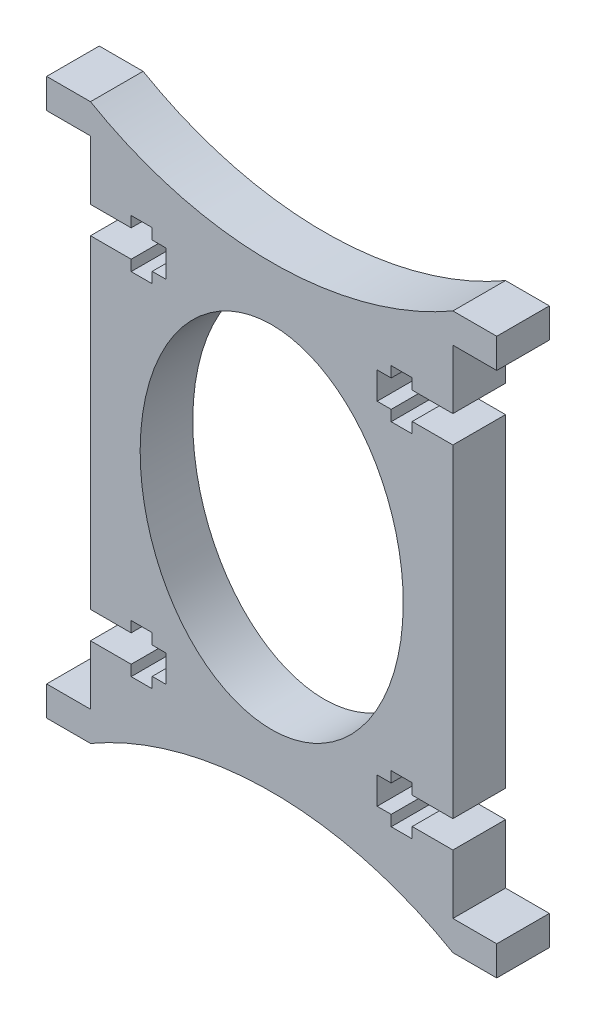
SolidWorks part; units mm, degrees
material "Acrylic (Medium-high impact)"
ref_plane "Front Plane" through (0, 0, 0) normal (0, 0, 1) x (1, 0, 0)
ref_plane "Top Plane" through (0, 0, 0) normal (0, 1, 0) x (1, 0, 0)
ref_plane "Right Plane" through (0, 0, 0) normal (1, 0, 0) x (0, 0, -1)
sketch "Sketch1" plane through (0, 0, 0) normal (0, 0, 1) x (1, 0, 0)
  line L0 (742.183, 459.4261) -> (700.8541, 459.4261) construction
  line L1 (737.5448, 439.4261) -> (742.183, 439.4261) construction
  line L2 (737.5448, 439.4261) -> (737.5448, 437.8782) construction
  line L3 (737.5448, 440.9739) -> (737.5448, 439.4261) construction
  line L4 (736.3448, 436.6538) -> (736.3448, 439.4261) construction
  line L5 (733.5448, 439.4261) -> (742.183, 439.4261) construction
  line L6 (736.3448, 442.1983) -> (736.3448, 439.4261) construction
  line L7 (735.1448, 436.6538) -> (737.5448, 436.6538)
  line L8 (700.8541, 459.4261) -> (700.8541, 440.9739)
  line L9 (706.6923, 442.1983) -> (706.6923, 439.4261) construction
  line L10 (735.1448, 442.1983) -> (737.5448, 442.1983)
  line L11 (733.5448, 440.9739) -> (733.5448, 437.8782)
  line L12 (742.183, 437.8782) -> (742.183, 431.1161)
  line L13 (742.183, 437.8782) -> (737.5448, 437.8782)
  line L14 (737.5448, 440.9739) -> (742.183, 440.9739)
  line L15 (747.183, 427.7361) -> (747.183, 431.1161)
  line L16 (742.183, 427.7361) -> (747.183, 427.7361)
  line L17 (709.4923, 439.4261) -> (700.8541, 439.4261) construction
  line L18 (707.8923, 436.6538) -> (707.8923, 437.8782)
  line L19 (707.8923, 440.9739) -> (709.4923, 440.9739)
  line L20 (707.8923, 437.8782) -> (709.4923, 437.8782)
  line L21 (707.8923, 440.9739) -> (707.8923, 442.1983)
  line L22 (706.6923, 436.6538) -> (706.6923, 439.4261) construction
  line L23 (705.4923, 436.6538) -> (705.4923, 437.8782)
  line L24 (705.4923, 440.9739) -> (705.4923, 442.1983)
  line L25 (705.4923, 440.9739) -> (705.4923, 439.4261) construction
  line L26 (705.4923, 439.4261) -> (705.4923, 437.8782) construction
  line L27 (695.8541, 431.1161) -> (700.8541, 431.1161)
  line L28 (700.8541, 427.7361) -> (695.8541, 427.7361)
  line L29 (695.8541, 427.7361) -> (695.8541, 431.1161)
  line L30 (705.4923, 440.9739) -> (700.8541, 440.9739)
  line L31 (700.8541, 437.8782) -> (705.4923, 437.8782)
  line L32 (700.8541, 437.8782) -> (700.8541, 431.1161)
  line L33 (705.4923, 439.4261) -> (700.8541, 439.4261) construction
  line L34 (709.4923, 440.9739) -> (709.4923, 437.8782)
  line L35 (747.183, 431.1161) -> (742.183, 431.1161)
  line L36 (737.5448, 440.9739) -> (737.5448, 442.1983)
  line L37 (737.5448, 436.6538) -> (737.5448, 437.8782)
  line L38 (735.1448, 440.9739) -> (735.1448, 442.1983)
  line L39 (735.1448, 437.8782) -> (733.5448, 437.8782)
  line L40 (735.1448, 440.9739) -> (733.5448, 440.9739)
  line L41 (735.1448, 436.6538) -> (735.1448, 437.8782)
  line L42 (742.183, 459.4261) -> (742.183, 440.9739)
  line L43 (705.4923, 479.4261) -> (700.8541, 479.4261) construction
  line L44 (707.8923, 442.1983) -> (705.4923, 442.1983)
  line L45 (705.4923, 479.4261) -> (705.4923, 480.9739) construction
  line L46 (705.4923, 477.8782) -> (705.4923, 479.4261) construction
  line L47 (706.6923, 482.1983) -> (706.6923, 479.4261) construction
  line L48 (709.4923, 479.4261) -> (700.8541, 479.4261) construction
  line L49 (706.6923, 476.6538) -> (706.6923, 479.4261) construction
  line L50 (736.3448, 476.6538) -> (736.3448, 479.4261) construction
  line L51 (733.5448, 479.4261) -> (742.183, 479.4261) construction
  line L52 (736.3448, 482.1983) -> (736.3448, 479.4261) construction
  line L53 (737.5448, 477.8782) -> (737.5448, 479.4261) construction
  line L54 (737.5448, 479.4261) -> (737.5448, 480.9739) construction
  line L55 (737.5448, 479.4261) -> (742.183, 479.4261) construction
  line L56 (707.8923, 482.1983) -> (705.4923, 482.1983)
  line L57 (707.8923, 476.6538) -> (705.4923, 476.6538)
  line L58 (742.183, 459.4261) -> (742.183, 477.8782)
  line L59 (735.1448, 482.1983) -> (735.1448, 480.9739)
  line L60 (721.5185, -540.5739) -> (721.5185, 49459.4261) construction
  line L61 (707.8923, 436.6538) -> (705.4923, 436.6538)
  line L62 (735.1448, 477.8782) -> (733.5448, 477.8782)
  line L63 (735.1448, 480.9739) -> (733.5448, 480.9739)
  line L64 (735.1448, 477.8782) -> (735.1448, 476.6538)
  line L65 (737.5448, 482.1983) -> (737.5448, 480.9739)
  line L66 (737.5448, 477.8782) -> (737.5448, 476.6538)
  line L67 (747.183, 487.7361) -> (742.183, 487.7361)
  line L68 (709.4923, 477.8782) -> (709.4923, 480.9739)
  line L69 (700.8541, 480.9739) -> (700.8541, 487.7361)
  line L70 (700.8541, 480.9739) -> (705.4923, 480.9739)
  line L71 (705.4923, 477.8782) -> (700.8541, 477.8782)
  line L72 (695.8541, 491.1161) -> (695.8541, 487.7361)
  line L73 (700.8541, 491.1161) -> (695.8541, 491.1161)
  line L74 (695.8541, 487.7361) -> (700.8541, 487.7361)
  line L75 (705.4923, 477.8782) -> (705.4923, 476.6538)
  line L76 (705.4923, 482.1983) -> (705.4923, 480.9739)
  line L77 (707.8923, 477.8782) -> (707.8923, 476.6538)
  line L78 (707.8923, 480.9739) -> (709.4923, 480.9739)
  line L79 (707.8923, 477.8782) -> (709.4923, 477.8782)
  line L80 (707.8923, 482.1983) -> (707.8923, 480.9739)
  line L81 (742.183, 491.1161) -> (747.183, 491.1161)
  line L82 (747.183, 491.1161) -> (747.183, 487.7361)
  line L83 (737.5448, 477.8782) -> (742.183, 477.8782)
  line L84 (742.183, 480.9739) -> (737.5448, 480.9739)
  line L85 (742.183, 480.9739) -> (742.183, 487.7361)
  line L86 (733.5448, 477.8782) -> (733.5448, 480.9739)
  line L87 (735.1448, 476.6538) -> (737.5448, 476.6538)
  line L88 (700.8541, 459.4261) -> (700.8541, 477.8782)
  line L89 (735.1448, 482.1983) -> (737.5448, 482.1983)
  line L90 (721.5185, 459.4261) -> (706.5185, 459.4261) construction
  line L91 (700.8541, 480.9739) -> (700.8541, 477.8782) construction
  line L92 (700.8541, 487.7361) -> (700.8541, 491.1161) construction
  line L93 (700.8541, 431.1161) -> (700.8541, 427.7361) construction
  line L94 (700.8541, 491.1161) -> (742.183, 491.1161) construction
  line L95 (700.8541, 427.7361) -> (742.183, 427.7361) construction
  line L96 (742.183, 480.9739) -> (742.183, 477.8782) construction
  line L97 (742.183, 440.9739) -> (742.183, 437.8782) construction
  arc A0 (700.8541, 491.1161) -> (742.183, 491.1161) centre (721.5185, 526.8562) ccw
  arc A1 (700.8541, 427.7361) -> (742.183, 427.7361) centre (721.5185, 391.996) cw
  ellipse E0 centre (721.5185, 459.4261) end of major axis (721.5185, 479.4261) minor radius 15
  point P38 (721.5185, 459.4261)
  point P102 (700.8541, 489.4261)
  point P103 (700.8541, 429.4261)
  dimension "D1" = 60
  dimension "D2" = 3.0957
  dimension "D3" = 3.38
  dimension "D4" = 10
  dimension "D5" = 1.6
  dimension "D7" = 2.4
  dimension "D8" = 1.2244
  dimension "D10" = 5
  dimension "D12" = 30
  dimension "D13" = 40
  dimension "D14" = 5.6644
  dimension "D15" = 4.6382
extrude "Boss-Extrude1" add sketch "Sketch1" along normal blind 6
